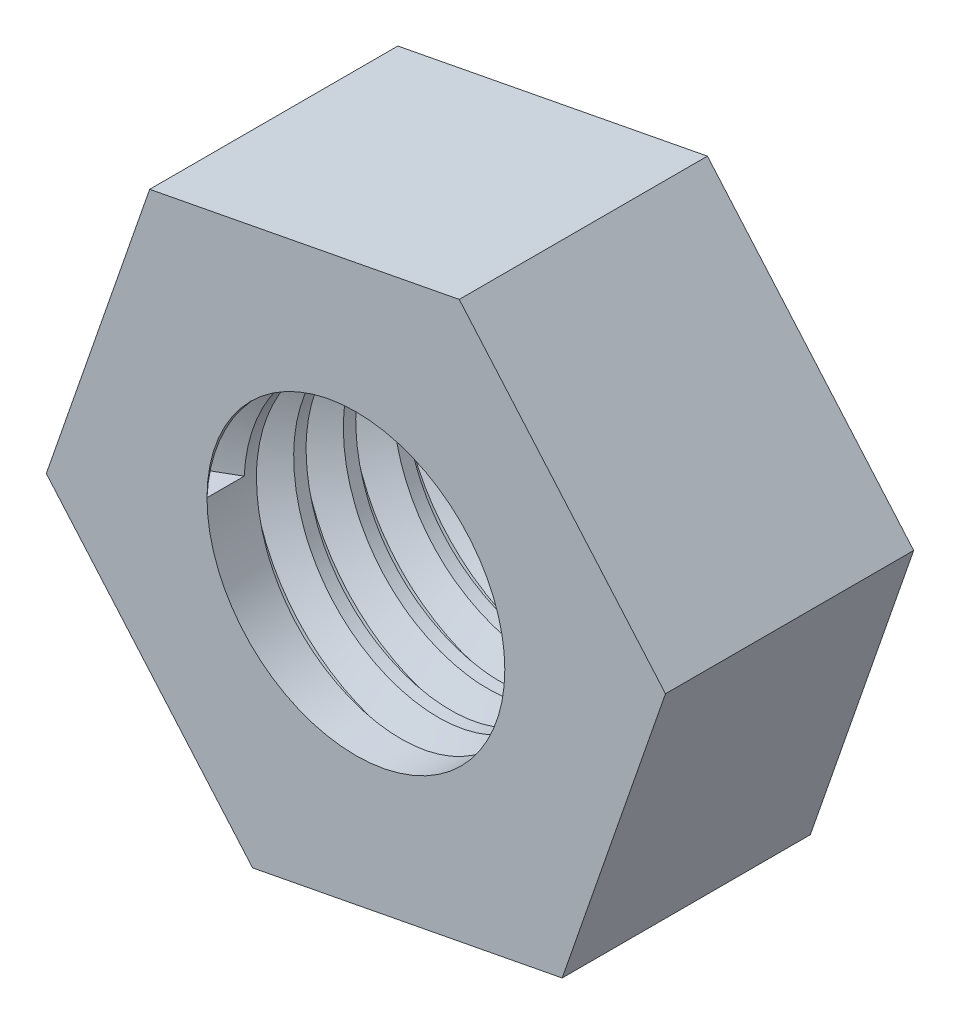
SolidWorks part; units mm, degrees
ref_plane "Front Plane" through (0, 0, 0) normal (0, 0, 1) x (1, 0, 0)
ref_plane "Top Plane" through (0, 0, 0) normal (0, 1, 0) x (1, 0, 0)
ref_plane "Right Plane" through (0, 0, 0) normal (1, 0, 0) x (0, 0, -1)
sketch "Sketch1" plane through (0, 0, 0) normal (0, 0, 1) x (1, 0, 0)
  line L1 (2.0777, -2.4014) -> (3.1185, 0.5986)
  line L2 (3.1185, 0.5986) -> (1.0408, 3)
  line L3 (1.0408, 3) -> (-2.0777, 2.4014)
  line L4 (-2.0777, 2.4014) -> (-3.1185, -0.5986)
  line L5 (-3.1185, -0.5986) -> (-1.0408, -3)
  line L6 (-1.0408, -3) -> (2.0777, -2.4014)
  circle A0 centre (0, 0) radius 2.75 construction
  dimension "D2" = 5.5
extrude "Boss-Extrude1" add sketch "Sketch1" along normal blind 2.5
sketch "Sketch2" plane through (0, 0, 2.5) normal (0, 0, 1) x (1, 0, 0)
  circle A0 centre (0, 0) radius 1.5
  dimension "D1" = 3
extrude "Cut-Extrude1" cut sketch "Sketch2" against normal through all
thread "Thread1" pitch 0.5 method cut profile "Thread Profile1" start angle 0, offset 0, length 0, pitch 0.5, diameter 3
ref_plane "Plane1" through (-1.5, 0, 2.5) normal (0, -1, 0) x (-1, 0, 0)
sketch "Thread Profile1" plane through (-1.5, 0, 2.5) normal (0, -1, 0) x (-1, 0, 0)
  line L0 (0, 0) -> (0, 0.5) construction
  line L1 (0, 0) -> (0.2706, 0.1562)
  line L2 (0.2706, 0.1562) -> (0.2706, 0.2187)
  line L3 (0.2706, 0.2187) -> (0, 0.375)
  line L4 (0.2706, 0.1875) -> (0, 0.1875) construction
  line L11 (0, 0) -> (0, 0.375)
  point P2 (0, 0)
  dimension "Pitch" = 0.5
  dimension "Profile_Angle" = 60
  dimension "Profile_Land" = 0.0625
  dimension "Profile_Height" = 0.2706
